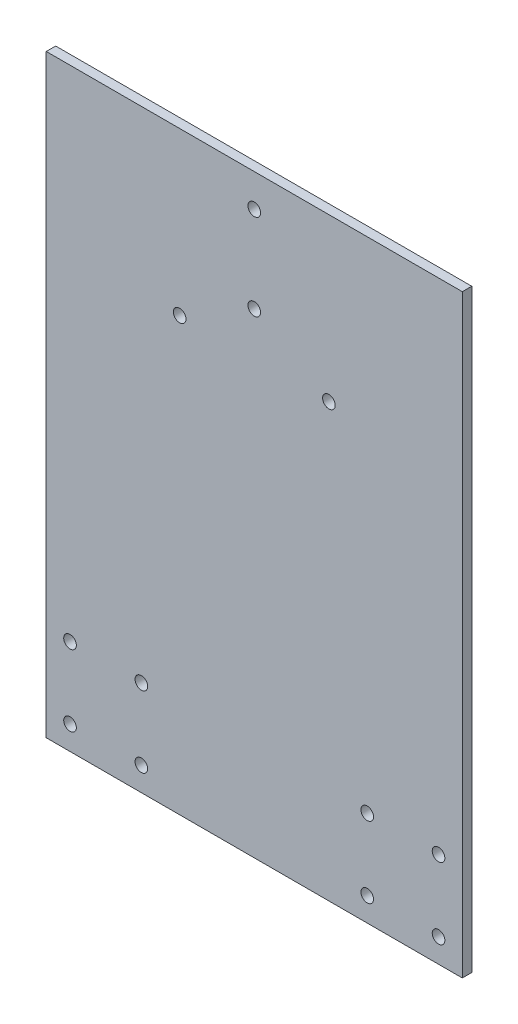
SolidWorks part; units mm, degrees
ref_plane "Front Plane" through (0, 0, 0) normal (0, 0, 1) x (1, 0, 0)
ref_plane "Top Plane" through (0, 0, 0) normal (0, 1, 0) x (1, 0, 0)
ref_plane "Right Plane" through (0, 0, 0) normal (1, 0, 0) x (0, 0, -1)
sketch "Sketch1" plane through (0, 0, 0) normal (0, 0, 1) x (1, 0, 0)
  line L0 (0, 100) -> (0, -100) construction
  line L1 (-70, -100) -> (70, -100)
  line L2 (-70, -100) -> (-70, 100)
  line L3 (-70, 100) -> (70, 100)
  line L4 (70, -100) -> (70, 100)
  line L5 (-70, -100) -> (70, 100) construction
  line L6 (-70, 100) -> (70, -100) construction
  line L7 (-50, -95.8304) -> (-50, -78.0714) construction
  line L10 (-62, -80) -> (-36.3402, -80) construction
  circle A0 centre (0, 60) radius 33.35 construction
  circle A1 centre (0, 60) radius 29 construction
  circle A2 centre (0, 89) radius 2.125
  circle A3 centre (25.1147, 45.5) radius 2.125
  circle A4 centre (-25.1147, 45.5) radius 2.125
  circle A10 centre (0, 60) radius 2.125
  circle A11 centre (-62, -92) radius 2.125
  circle A12 centre (-38, -92) radius 2.125
  circle A13 centre (-38, -68) radius 2.125
  circle A14 centre (-62, -68) radius 2.125
  circle A15 centre (38, -92) radius 2.125
  circle A16 centre (62, -92) radius 2.125
  circle A17 centre (62, -68) radius 2.125
  circle A18 centre (38, -68) radius 2.125
  point P0 (0, 0)
  point P19 (0, 60)
  dimension "D3" = 66.7
  dimension "D4" = 40
  dimension "D5" = 58
  dimension "D6" = 4.25
  dimension "D8" = 4.25
  dimension "D9" = 8
  dimension "D10" = 8
  dimension "D12" = 4.25
  dimension "D1" = 140
  dimension "D2" = 200
  dimension "D11" = 12
  dimension "D13" = 12
  dimension "D7" = 3
extrude "Boss-Extrude1" add sketch "Sketch1" along normal blind 3.175
